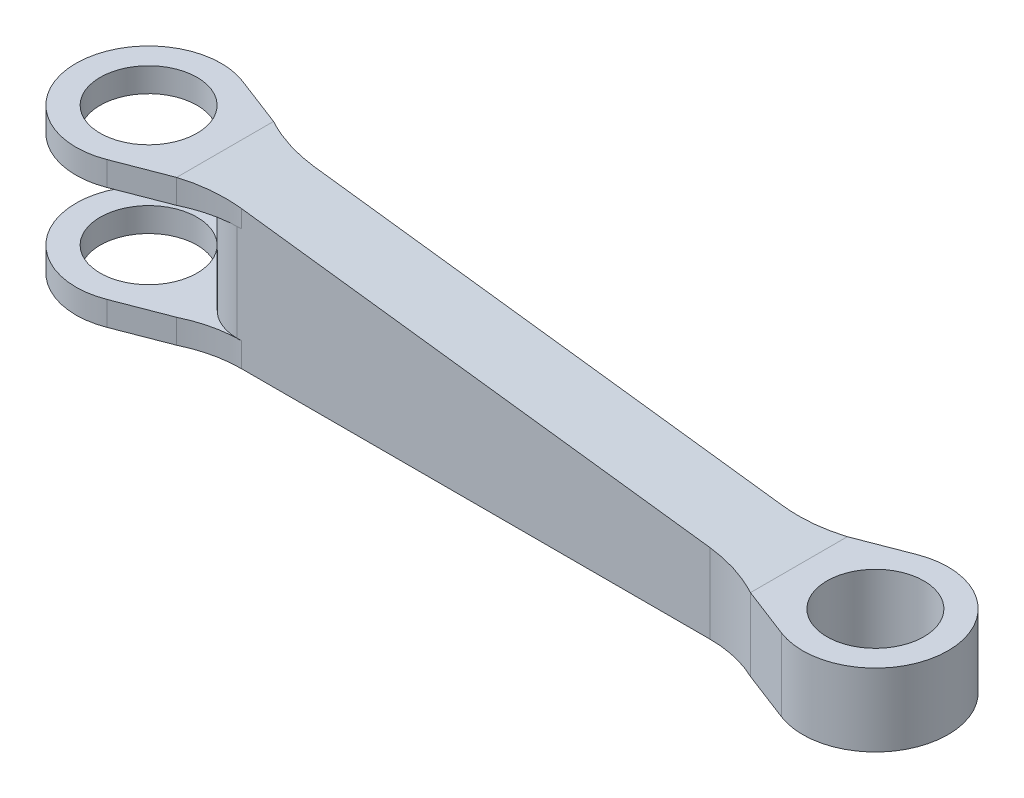
SolidWorks part; units mm, degrees
ref_plane "Front Plane" through (0, 0, 0) normal (0, 0, 1) x (1, 0, 0)
ref_plane "Top Plane" through (0, 0, 0) normal (0, 1, 0) x (1, 0, 0)
ref_plane "Right Plane" through (0, 0, 0) normal (1, 0, 0) x (0, 0, -1)
sketch "Sketch1" plane through (0, 0, 0) normal (0, 1, 0) x (1, 0, 0)
  line L0 (0, 0) -> (76.2, 0) construction
  line L1 (38.1, -22.8401) -> (38.1, 22.8401) construction
  line L2 (2.7357, 7.112) -> (8.0183, 5.08)
  line L3 (8.0183, 5.08) -> (8.0183, 3.81)
  line L4 (8.0183, 3.81) -> (68.1817, 3.81)
  line L5 (68.1817, 3.81) -> (68.1817, 5.08)
  line L6 (68.1817, 5.08) -> (73.4643, 7.112)
  line L7 (68.1817, -5.08) -> (73.4643, -7.112)
  line L8 (68.1817, -3.81) -> (68.1817, -5.08)
  line L9 (8.0183, -3.81) -> (68.1817, -3.81)
  line L10 (8.0183, -5.08) -> (8.0183, -3.81)
  line L11 (2.7357, -7.112) -> (8.0183, -5.08)
  circle A0 centre (0, 0) radius 5.08
  circle A1 centre (76.2, 0) radius 5.08
  arc A2 (2.7357, 7.112) -> (2.7357, -7.112) centre (0, 0) ccw
  arc A3 (73.4643, 7.112) -> (73.4643, -7.112) centre (76.2, 0) cw
  point P16 (38.1, 0)
  dimension "D1" = 10.16
  dimension "D3" = 2.54
  dimension "D4" = 2.54
  dimension "D2" = 76.2
  dimension "D5" = 3.81
  dimension "D6" = 1.27
  dimension "D7" = 2.032
extrude "Boss-Extrude1" add sketch "Sketch1" along normal mid plane 15.24
ref_plane "Plane1" through (0, 0, 13.97) normal (0, 0, 1) x (1, 0, 0)
sketch "Sketch2" plane through (0, 0, 13.97) normal (0, 0, 1) x (1, 0, 0)
  line L0 (-7.62, 7.62) -> (8.0183, 7.62) construction
  line L1 (8.0183, 7.62) -> (68.1817, 7.62) construction
  line L2 (8.0183, 7.62) -> (68.1817, 0)
  line L3 (68.1817, 0) -> (83.82, 0)
  line L4 (83.82, -7.62) -> (83.82, 7.62) construction
  line L5 (0, 0) -> (40.6246, 0) construction
  line L6 (-7.62, 7.62) -> (-7.62, -7.62) construction
  line L7 (-7.62, 5.08) -> (8.0183, 5.08)
  line L8 (-7.62, 5.08) -> (-7.62, -5.08)
  line L9 (-7.62, -5.08) -> (8.0183, -5.08)
  line L10 (8.0183, 5.08) -> (8.0183, -5.08)
  line L11 (8.0183, 7.62) -> (8.0183, -7.62) construction
  line L12 (8.0183, 7.62) -> (83.82, 7.62)
  line L13 (83.82, 7.62) -> (83.82, 0)
  line L15 (-7.62, -7.62) -> (8.0183, -7.62) construction
  point P22 (-7.62, 0)
  dimension "D1" = 7.62
  dimension "D2" = 2.54
extrude "Cut-Extrude1" cut sketch "Sketch2" against normal through all
fillet "Fillet1" radius 12.7 6 edges at (68.1817, -3.81, 3.81) (68.1817, -3.81, -3.81) (8.0183, -6.35, -3.81) (8.0183, 6.35, -3.81) (8.0183, -6.35, 3.81) (8.0183, 6.35, 3.81)
fillet "Fillet2" radius 5.08 2 edges at (8.0183, 0, -3.81) (8.0183, 0, 3.81)
